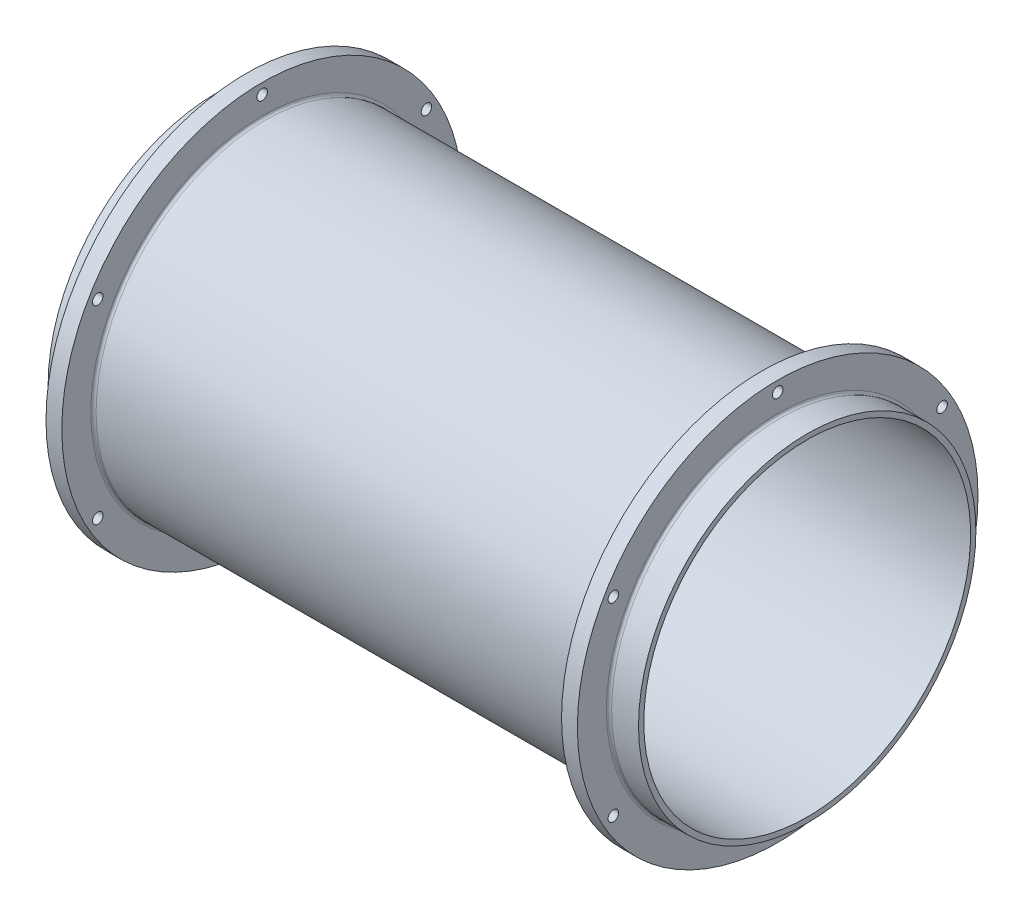
SolidWorks part; units mm, degrees
material "Acrylic (Medium-high impact)"
ref_plane "Front Plane" through (0, 0, 0) normal (0, 0, 1) x (1, 0, 0)
ref_plane "Top Plane" through (0, 0, 0) normal (0, 1, 0) x (1, 0, 0)
ref_plane "Right Plane" through (0, 0, 0) normal (1, 0, 0) x (0, 0, -1)
sketch "Sketch1" plane through (0, 0, 0) normal (0, 0, 1) x (1, 0, 0)
  line L0 (0, 0) -> (32.6869, 0) construction
  line L1 (177.8, -101.6) -> (-177.8, -101.6)
  line L2 (177.8, -101.6) -> (177.8, 101.6)
  line L3 (177.8, 101.6) -> (-177.8, 101.6)
  line L4 (-177.8, -101.6) -> (-177.8, 101.6)
  line L5 (177.8, -101.6) -> (-177.8, 101.6) construction
  line L6 (177.8, 101.6) -> (-177.8, -101.6) construction
  line L7 (177.8, -98.425) -> (-177.8, -98.425)
  line L8 (177.8, -98.425) -> (177.8, 98.425)
  line L9 (177.8, 98.425) -> (-177.8, 98.425)
  line L10 (-177.8, -98.425) -> (-177.8, 98.425)
  line L11 (177.8, -98.425) -> (-177.8, 98.425) construction
  line L12 (177.8, 98.425) -> (-177.8, -98.425) construction
  line L14 (-160.02, -120.65) -> (-150.495, -120.65)
  line L15 (-160.02, -120.65) -> (-160.02, 120.65)
  line L16 (-160.02, 120.65) -> (-150.495, 120.65)
  line L17 (-150.495, -120.65) -> (-150.495, 120.65)
  line L18 (-160.02, -120.65) -> (-150.495, 120.65) construction
  line L19 (-160.02, 120.65) -> (-150.495, -120.65) construction
  line L20 (150.495, -120.65) -> (160.02, -120.65)
  line L21 (150.495, -120.65) -> (150.495, 120.65)
  line L22 (150.495, 120.65) -> (160.02, 120.65)
  line L23 (160.02, -120.65) -> (160.02, 120.65)
  line L24 (150.495, -120.65) -> (160.02, 120.65) construction
  line L25 (150.495, 120.65) -> (160.02, -120.65) construction
  point P0 (0, 0)
  point P6 (0, 0)
  point P12 (-155.2575, 0)
  point P18 (155.2575, 0)
  dimension "D1" = 3.175
  dimension "D2" = 355.6
  dimension "D3" = 203.2
  dimension "D4" = 9.525
  dimension "D5" = 9.525
  dimension "D6" = 17.78
  dimension "D7" = 17.78
  dimension "D8" = 241.3
revolve "Revolve1" add sketch "Sketch1" angle 360 about L0
sketch "Sketch2" plane through (160.02, 0, 0) normal (1, 0, 0) x (0, 0, -1)
  circle A0 centre (0, 114.3) radius 3.175
  circle A1 centre (98.9867, 57.15) radius 3.175
  circle A2 centre (98.9867, -57.15) radius 3.175
  circle A3 centre (0, -114.3) radius 3.175
  circle A4 centre (-98.9867, -57.15) radius 3.175
  circle A5 centre (-98.9867, 57.15) radius 3.175
  point P15 (0, 0)
  dimension "D2" = 6.35
  dimension "D1" = 114.3
  dimension "D3" = 6
extrude "Cut-Extrude1" cut sketch "Sketch2" against normal through all
fillet "Solvent Weld" radius 1.5875 4 edges at (160.02, 0, 101.6) (150.495, 0, 101.6) (-160.02, 0, 101.6) (-150.495, 0, 101.6)
